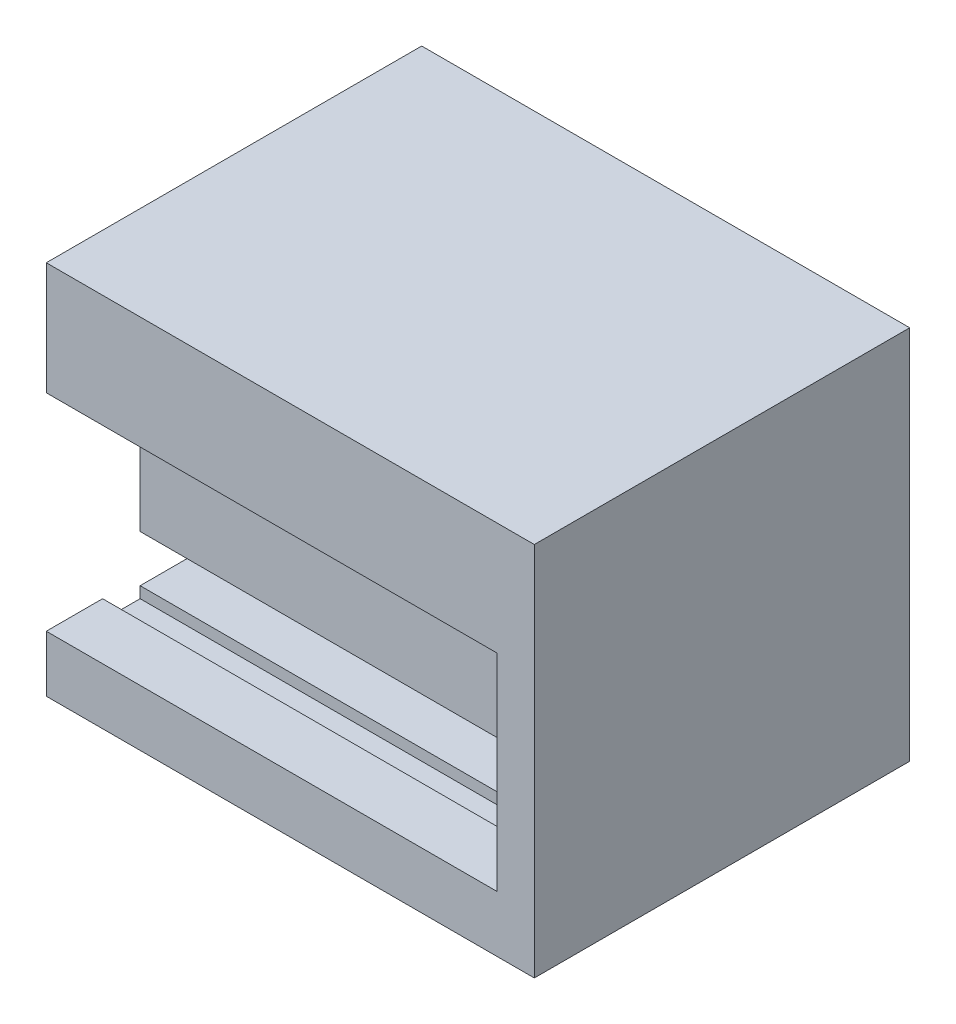
SolidWorks part; units mm, degrees
ref_plane "Front Plane" through (0, 0, 0) normal (0, 0, 1) x (1, 0, 0)
ref_plane "Top Plane" through (0, 0, 0) normal (0, 1, 0) x (1, 0, 0)
ref_plane "Right Plane" through (0, 0, 0) normal (1, 0, 0) x (0, 0, -1)
sketch "Sketch1" plane through (0, 0, 0) normal (0, 0, 1) x (1, 0, 0)
  line L1 (-19.4845, 15.0952) -> (13.5355, 15.0952)
  line L2 (-19.4845, 15.0952) -> (-19.4845, -10.3048)
  line L3 (-19.4845, -10.3048) -> (13.5355, -10.3048)
  line L4 (13.5355, 15.0952) -> (13.5355, -10.3048)
  line L5 (-16.9445, 12.5552) -> (10.9955, 12.5552)
  line L6 (-16.9445, 12.5552) -> (-16.9445, -7.7648)
  line L7 (-16.9445, -7.7648) -> (10.9955, -7.7648)
  line L8 (10.9955, 12.5552) -> (10.9955, -7.7648)
  line L9 (-10.912, -3.8278) -> (4.963, -3.8278)
  line L10 (-10.912, -3.8278) -> (-10.912, -7.0028)
  line L11 (-10.912, -7.0028) -> (4.963, -7.0028)
  line L12 (4.963, -3.8278) -> (4.963, -7.0028)
  line L13 (-16.9445, 7.4752) -> (10.9955, 7.4752)
  line L14 (-16.9445, 7.4752) -> (-16.9445, -6.4948)
  line L15 (-16.9445, -6.4948) -> (10.9955, -6.4948)
  line L16 (10.9955, 7.4752) -> (10.9955, -6.4948)
  point P16 (-2.9745, 15.0952)
  point P17 (-2.9745, 12.5552)
  point P18 (-2.9745, -3.8278)
  point P19 (10.9955, 2.3952)
  point P20 (13.5355, 2.3952)
  dimension "D1" = 3.175
  dimension "D2" = 25.4
  dimension "D3" = 33.02
  dimension "D4" = 27.94
  dimension "D5" = 15.875
  dimension "D6" = 20.32
  dimension "D7" = 13.97
  dimension "D8" = 1.27
  dimension "D9" = 3.937
extrude "Boss-Extrude1" add sketch "Sketch1" against normal blind 25.4 contours L4 L3 L2 L1
extrude "Cut-Extrude2" cut sketch "Sketch1<4>" against normal blind 2.54 from offset 3.81 contours L15 L6 L7 L8 L12 L11 L10 | L15 L10 L11 L12 | L6 L13 L8 L5 region at (-2.9745, 10.0152, 0) region at (-2.9745, -7.2419, 0) region at (-2.9745, -6.7488, 0) offset against normal yes
sketch "Sketch1<4>" plane through (0, 0, 0) normal (0, 0, 1) x (1, 0, 0) same geometry as "Sketch1"
extrude "Cut-Extrude1" cut sketch "Sketch1<3>" against normal blind 6.35 contours L14 L13 L16 L15
sketch "Sketch1<3>" plane through (0, 0, 0) normal (0, 0, 1) x (1, 0, 0) same geometry as "Sketch1"
extrude "Cut-Extrude3" cut sketch "Sketch1<5>" against normal blind 19.05 from offset 6.35 contours L10 L15 L12 L9 | L15 L10 L11 L12 region at (-2.9745, -6.7488, 0) region at (-2.9745, -5.1613, 0) offset against normal yes
sketch "Sketch1<5>" plane through (0, 0, 0) normal (0, 0, 1) x (1, 0, 0) same geometry as "Sketch1"
sketch "Sketch4" plane through (-10.912, 0, 0) normal (1, 0, 0) x (0, 0, -1)
  line L0 (6.35, -3.8278) -> (6.35, -7.0028) construction
  line L1 (6.35, -7.0028) -> (19.05, -7.0028)
  line L2 (6.35, -7.0028) -> (6.35, -3.8278)
  line L3 (6.35, -3.8278) -> (19.05, -3.8278)
  line L4 (19.05, -7.0028) -> (19.05, -3.8278)
  line L5 (6.35, -7.5198) -> (4.3279, -7.5198)
  line L6 (4.3279, -7.5198) -> (4.3279, -6.6113)
  line L7 (4.3279, -6.6113) -> (0.1851, -6.6113)
  line L8 (0.1851, -6.6113) -> (0.1851, 9.4573)
  line L9 (0.1851, 9.4573) -> (1.6597, 9.4573)
  line L10 (1.6597, 9.4573) -> (1.6597, 9.8293)
  line L11 (1.6597, 9.8293) -> (6.35, 9.8293)
  line L12 (6.35, 9.8293) -> (6.35, -3.8278)
  line L14 (6.35, -7.5198) -> (6.35, -7.0028)
  point P4 (0, 0)
  point P14 (0, 0)
  point P18 (0, 0)
  point P19 (0, 0)
  point P20 (0.3329, -6.5508)
  point P21 (0, 0)
  point P22 (0.7762, -6.6113)
  dimension "D2" = 12.7
extrude "Cut-Extrude4" cut sketch "Sketch4" against normal blind 19.05 contours L2 L1 L4 L3
sketch "Sketch7" plane through (-16.9445, 0, 0) normal (1, 0, 0) x (0, 0, -1)
  line L0 (0, 7.4752) -> (3.81, 7.4752)
  line L2 (3.81, 7.4752) -> (3.81, 12.5552)
  line L3 (3.81, 12.5552) -> (6.35, 12.5552)
  line L4 (6.35, 12.5552) -> (6.35, -7.7648)
  line L5 (6.35, -7.7648) -> (3.81, -7.7648)
  line L6 (3.81, -7.7648) -> (3.81, -6.4948)
  line L7 (3.81, -6.4948) -> (0, -6.4948)
  line L8 (0, -6.4948) -> (0, 7.4752)
  point P3 (0, 0)
  point P5 (0, 0)
  point P13 (0, 0)
  point P15 (0, 0)
extrude "Cut-Extrude5" cut sketch "Sketch7" against normal blind 6.35 contours L2 L3 L4 L5 L6 L7 L8 L0
